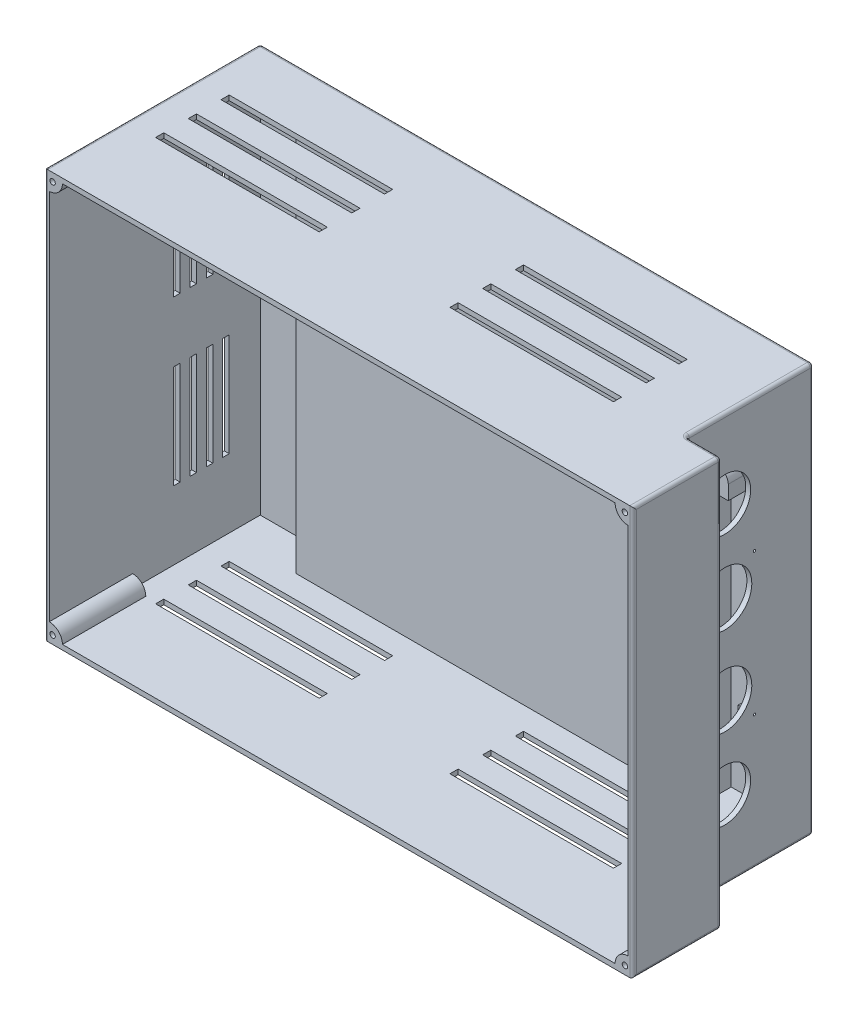
SolidWorks part; units mm, degrees
ref_plane "前视基准面" through (0, 0, 0) normal (0, 0, 1) x (1, 0, 0)
ref_plane "上视基准面" through (0, 0, 0) normal (0, 1, 0) x (1, 0, 0)
ref_plane "右视基准面" through (0, 0, 0) normal (1, 0, 0) x (0, 0, -1)
sketch "草图2" plane through (0, 0, 0) normal (0, 0, 1) x (1, 0, 0)
  line L1 (-90, 62.5) -> (90, 62.5)
  line L2 (-90, 62.5) -> (-90, -62.5)
  line L3 (-90, -62.5) -> (90, -62.5)
  line L4 (90, 62.5) -> (90, -62.5)
  line L5 (-90, 62.5) -> (90, -62.5) construction
  line L6 (-90, -62.5) -> (90, 62.5) construction
  point P0 (0, 0)
  dimension "D1" = 180
  dimension "D2" = 125
extrude "凸台-拉伸1" add sketch "草图2" along normal blind 66
sketch "草图3" plane through (0, 0, 0) normal (0, 0, -1) x (-1, 0, 0)
  line L0 (66, 59.5) -> (66, -59.5)
  line L1 (66, -59.5) -> (-54, -59.5)
  line L3 (66, 59.5) -> (-54, 59.5)
  line L4 (-54, -59.5) -> (-54, 59.5)
  line L5 (-90, 62.5) -> (90, 62.5) construction
  line L7 (90, -62.5) -> (-90, -62.5) construction
  line L9 (-90, -62.5) -> (-90, 62.5) construction
  line L11 (90, 62.5) -> (90, -62.5) construction
  dimension "D1" = 3
  dimension "D2" = 24
  dimension "D3" = 3
  dimension "D4" = 36
extrude "切除-拉伸1" cut sketch "草图3" against normal blind 10
sketch "草图4" plane through (90, 0, 0) normal (1, 0, 0) x (0, 0, -1)
  line L0 (-39, -62.5) -> (-39, 62.5)
  line L1 (-66, 61.5) -> (-66, -61.5) construction
  line L2 (-66, 62.5) -> (0, 62.5) construction
  line L4 (0, -62.5) -> (0, 62.5)
  line L6 (-66, 62.5) -> (-66, -62.5)
  line L9 (0, 62.5) -> (-39, 62.5)
  line L11 (-39, -62.5) -> (0, -62.5)
  line L14 (0, -62.5) -> (0, 62.5)
  line L15 (0, 62.5) -> (-66, 62.5)
  line L16 (-66, -62.5) -> (0, -62.5)
  dimension "D2" = 27
  dimension "D1" = 0
extrude "切除-拉伸2" cut sketch "草图4" against normal offset from surface (10.8 mm away) 2
shell "抽壳1" thickness 1.5 removed face at (0, 0, 66)
sketch "草图6" plane through (79.2, 0, 0) normal (1, 0, 0) x (0, 0, -1)
  line L1 (-16.0647, -23.6651) -> (-20.0647, -23.6651)
  line L2 (-16.0647, -23.6651) -> (-16.0647, -19.6651)
  line L3 (-16.0647, -19.6651) -> (-20.0647, -19.6651)
  line L4 (-20.0647, -23.6651) -> (-20.0647, -19.6651)
  line L5 (-34.2212, -23.6651) -> (-38.2212, -23.6651)
  line L6 (-34.2212, -23.6651) -> (-34.2212, -19.6651)
  line L7 (-34.2212, -19.6651) -> (-38.2212, -19.6651)
  line L8 (-38.2212, -23.6651) -> (-38.2212, -19.6651)
  line L9 (-34.2212, 19.6651) -> (-38.2212, 19.6651)
  line L10 (-34.2212, 19.6651) -> (-34.2212, 23.6651)
  line L11 (-34.2212, 23.6651) -> (-38.2212, 23.6651)
  line L12 (-38.2212, 19.6651) -> (-38.2212, 23.6651)
  line L13 (-16.0647, 19.6651) -> (-20.0647, 19.6651)
  line L14 (-16.0647, 19.6651) -> (-16.0647, 23.6651)
  line L15 (-16.0647, 23.6651) -> (-20.0647, 23.6651)
  line L16 (-20.0647, 19.6651) -> (-20.0647, 23.6651)
  arc A0 (-18.5647, 21.6651) -> (-17.5647, 21.6651) centre (-18.0647, 21.6651) ccw construction
  arc A1 (-17.5647, 21.6651) -> (-18.5647, 21.6651) centre (-18.0647, 21.6651) ccw construction
  arc A2 (-35.7212, 21.6651) -> (-36.7212, 21.6651) centre (-36.2212, 21.6651) ccw construction
  arc A3 (-36.7212, 21.6651) -> (-35.7212, 21.6651) centre (-36.2212, 21.6651) ccw construction
  arc A4 (-36.7212, -21.6651) -> (-35.7212, -21.6651) centre (-36.2212, -21.6651) ccw construction
  arc A5 (-18.5647, -21.6651) -> (-17.5647, -21.6651) centre (-18.0647, -21.6651) ccw construction
  dimension "D10" = 2
  dimension "D1" = 2
  dimension "D2" = 2
  dimension "D3" = 2
  dimension "D4" = 2
  dimension "D5" = 4
  dimension "D6" = 2
  dimension "D7" = 4
  dimension "D8" = 2
  dimension "D9" = 2
  dimension "D11" = 4
  dimension "D12" = 4
  dimension "D13" = 2
  dimension "D14" = 2
  dimension "D15" = 4
  dimension "D16" = 4
extrude "凸台-拉伸2" add sketch "草图6" against normal up to surface (3 mm away)
sketch "草图7" plane through (79.2, 0, 0) normal (1, 0, 0) x (0, 0, -1)
  circle A0 centre (-27.143, -13.5) radius 8.25
  circle A1 centre (-27.143, 13.5) radius 8.25
  circle A2 centre (-18.0647, -21.6651) radius 0.375
  circle A3 centre (-18.0647, 21.6651) radius 0.375
  circle A4 centre (-36.2212, 21.6651) radius 0.375
  circle A5 centre (-36.2212, -21.6651) radius 0.375
  arc A6 (-19.143, -13.5) -> (-35.143, -13.5) centre (-27.143, -13.5) ccw construction
  circle A7 centre (-27.143, 38.5) radius 7.9
  circle A8 centre (-27.143, 38.5) radius 7.65 construction
  circle A9 centre (-27.143, -38.5) radius 7.9
  dimension "D1" = 0.75
  dimension "D2" = 0.25
  dimension "D3" = 0.25
extrude "切除-拉伸3" cut sketch "草图7" against normal up to next
sketch "草图8" plane through (0, -62.5, 0) normal (0, -1, 0) x (1, 0, 0)
  line L0 (-90, 66) -> (90, 66) construction
  line L1 (-81, 41) -> (-31, 41)
  line L2 (-81, 41) -> (-81, 38.5)
  line L3 (-81, 38.5) -> (-31, 38.5)
  line L4 (-31, 41) -> (-31, 38.5)
  line L5 (-90, 66) -> (-90, 0) construction
  line L6 (9, 41) -> (59, 41)
  line L7 (9, 41) -> (9, 38.5)
  line L8 (9, 38.5) -> (59, 38.5)
  line L9 (59, 41) -> (59, 38.5)
  line L10 (9, 31) -> (59, 31)
  line L11 (9, 31) -> (9, 28.5)
  line L12 (9, 28.5) -> (59, 28.5)
  line L13 (59, 31) -> (59, 28.5)
  line L14 (9, 21) -> (59, 21)
  line L15 (9, 21) -> (9, 18.5)
  line L16 (9, 18.5) -> (59, 18.5)
  line L17 (59, 21) -> (59, 18.5)
  line L18 (-81, 31) -> (-31, 31)
  line L19 (-81, 31) -> (-81, 28.5)
  line L20 (-81, 28.5) -> (-31, 28.5)
  line L21 (-31, 31) -> (-31, 28.5)
  line L22 (-81, 21) -> (-31, 21)
  line L23 (-81, 21) -> (-81, 18.5)
  line L24 (-81, 18.5) -> (-31, 18.5)
  line L25 (-31, 21) -> (-31, 18.5)
  dimension "D1" = 2.5
  dimension "D2" = 25
  dimension "D3" = 9
  dimension "D4" = 50
  dimension "D5" = 2
  dimension "D6" = 3
extrude "切除-拉伸4" cut sketch "草图8" against normal up to surface (125 mm away) and the other way through all up to face at (26.4, 62.5, 35)
sketch "草图9" plane through (0, 0, 66) normal (0, 0, 1) x (1, 0, 0)
  line L1 (-88.5, 61) -> (-84.5, 61)
  line L2 (-88.5, 61) -> (-88.5, 57)
  line L5 (0, 0) -> (0, 36.715) construction
  line L6 (0, 0) -> (38.7304, 0) construction
  line L7 (-88.5, -61) -> (-88.5, -57)
  line L8 (-88.5, -61) -> (-84.5, -61)
  line L9 (88.5, -61) -> (84.5, -61)
  line L10 (88.5, -61) -> (88.5, -57)
  line L11 (88.5, 61) -> (88.5, 57)
  line L12 (88.5, 61) -> (84.5, 61)
  circle A0 centre (-87.5, 60) radius 0.825
  arc A1 (-84.5, 61) -> (-88.5, 57) centre (-88.5, 61) cw
  arc A2 (-84.5, -61) -> (-88.5, -57) centre (-88.5, -61) ccw
  circle A3 centre (-87.5, -60) radius 0.825
  circle A4 centre (87.5, -60) radius 0.825
  arc A5 (84.5, -61) -> (88.5, -57) centre (88.5, -61) cw
  arc A6 (84.5, 61) -> (88.5, 57) centre (88.5, 61) ccw
  circle A7 centre (87.5, 60) radius 0.825
  dimension "D1" = 1.65
  dimension "D2" = 1
  dimension "D3" = 1
  dimension "D4" = 4
extrude "凸台-拉伸3" add sketch "草图9" against normal up to surface (25.5 mm away) up to face at (83.1, 0, 40.5)
sketch "草图10" plane through (0, 0, 1.5) normal (0, 0, 1) x (1, 0, 0)
  line L0 (77.7, -61) -> (77.7, 61) construction
  line L1 (77.7, 50.5757) -> (70.499, 50.5757)
  line L2 (77.7, 50.5757) -> (77.7, 61)
  line L3 (77.7, 61) -> (70.499, 61)
  line L4 (70.499, 50.5757) -> (70.499, 61)
  line L5 (84.5, 61) -> (-84.5, 61) construction
  line L6 (55.5, 61) -> (55.5, -61) construction
  line L7 (62.513, 50.5757) -> (55.5, 50.5757)
  line L8 (62.513, 50.5757) -> (62.513, 61)
  line L9 (62.513, 61) -> (55.5, 61)
  line L10 (55.5, 50.5757) -> (55.5, 61)
  line L11 (62.513, 22.2546) -> (55.5, 22.2546)
  line L12 (62.513, 22.2546) -> (62.513, 29.6276)
  line L13 (62.513, 29.6276) -> (55.5, 29.6276)
  line L14 (55.5, 22.2546) -> (55.5, 29.6276)
  line L16 (77.7, 22.2546) -> (70.499, 22.2546)
  line L17 (77.7, 22.2546) -> (77.7, 29.6276)
  line L18 (77.7, 29.6276) -> (70.499, 29.6276)
  line L19 (70.499, 22.2546) -> (70.499, 29.6276)
  arc A0 (73.999, 27.2546) -> (73.999, 25.2546) centre (73.999, 26.2546) ccw construction
  arc A1 (59.013, 25.1276) -> (59.013, 27.1276) centre (59.013, 26.1276) ccw construction
  arc A2 (59.013, 27.1276) -> (59.013, 25.1276) centre (59.013, 26.1276) ccw construction
  arc A4 (74.126, 53.5757) -> (74.126, 55.5757) centre (74.126, 54.5757) ccw construction
  circle A5 centre (74.126, 54.5757) radius 0.825
  circle A6 centre (59.14, 54.5757) radius 0.825
  circle A7 centre (59.013, 26.1276) radius 0.825
  circle A8 centre (73.999, 26.2546) radius 0.825
  dimension "D7" = 1.65
  dimension "D6" = 1.65
  dimension "D8" = 1.65
  dimension "D9" = 1.65
  dimension "D1" = 4
  dimension "D2" = 3.5
  dimension "D3" = 3.5
  dimension "D4" = 3.5
  dimension "D5" = 4
extrude "开关螺孔凸台-拉伸4" add sketch "草图10" along normal up to surface (7.8999 mm away)
sketch "草图11" plane through (0, 0, 0) normal (0, 0, -1) x (-1, 0, 0)
  circle A0 centre (-66.76, 36.1607) radius 6.1
  circle A5 centre (-65.482, 49.2417) radius 2.6
  dimension "D1" = 12.2
  dimension "D2" = 5.2
extrude "切除-拉伸5" cut sketch "草图11" against normal up to next
fillet "圆角1" radius 3 4 edges at (62.513, 29.6276, 5.45) (62.513, 50.5757, 5.45) (70.499, 29.6276, 5.45) (70.499, 50.5757, 5.45)
fillet "圆角2" radius 1 26 edges at (90, 0, 66) (90, 0, 39) (79.2, 0, 39) (-90, 0, 66) (-90, -62.5, 33) (90, -62.5, 52.5) (84.6, -62.5, 39) (79.2, -62.5, 19.5) (-90, 62.5, 33) (79.2, 62.5, 19.5) (84.6, 62.5, 39) (90, 62.5, 52.5) (-5.4, 62.5, 0) (-90, 0, 0) (-5.4, -62.5, 0) (79.2, 0, 0) (-66, 0, 0) (-6, 59.5, 0) (54, 0, 0) (-6, -59.5, 0) (62.882, 49.2417, 0) (60.66, 36.1607, 0) (-6, 59.5, 10) (-66, 0, 10) (-6, -59.5, 10) (54, 0, 10)
sketch "草图12" plane through (-90, 0, 0) normal (-1, 0, 0) x (0, 0, 1)
  line L0 (1, 61.5) -> (1, -61.5) construction
  line L1 (11, 41.5) -> (13, 41.5)
  line L2 (11, 41.5) -> (11, 10)
  line L3 (11, 10) -> (13, 10)
  line L4 (13, 41.5) -> (13, 10)
  line L5 (65, 61.5) -> (1, 61.5) construction
  line L6 (16, 41.5) -> (18, 41.5)
  line L7 (16, 41.5) -> (16, 10)
  line L8 (16, 10) -> (18, 10)
  line L9 (18, 41.5) -> (18, 10)
  line L10 (21, 41.5) -> (23, 41.5)
  line L11 (21, 41.5) -> (21, 10)
  line L12 (21, 10) -> (23, 10)
  line L13 (23, 41.5) -> (23, 10)
  line L14 (26, 41.5) -> (28, 41.5)
  line L15 (26, 41.5) -> (26, 10)
  line L16 (26, 10) -> (28, 10)
  line L17 (28, 41.5) -> (28, 10)
  line L18 (16, -8.5) -> (18, -8.5)
  line L19 (16, -8.5) -> (16, -40)
  line L20 (16, -40) -> (18, -40)
  line L21 (18, -8.5) -> (18, -40)
  line L22 (21, -8.5) -> (23, -8.5)
  line L23 (21, -8.5) -> (21, -40)
  line L24 (21, -40) -> (23, -40)
  line L25 (23, -8.5) -> (23, -40)
  line L26 (26, -8.5) -> (28, -8.5)
  line L27 (26, -8.5) -> (26, -40)
  line L28 (26, -40) -> (28, -40)
  line L29 (28, -8.5) -> (28, -40)
  line L30 (11, -8.5) -> (13, -8.5)
  line L31 (11, -8.5) -> (11, -40)
  line L32 (11, -40) -> (13, -40)
  line L33 (13, -8.5) -> (13, -40)
  dimension "D1" = 2
  dimension "D2" = 31.5
  dimension "D3" = 10
  dimension "D4" = 20
  dimension "D5" = 4
  dimension "D6" = 2
extrude "切除-拉伸6" cut sketch "草图12" against normal up to next
